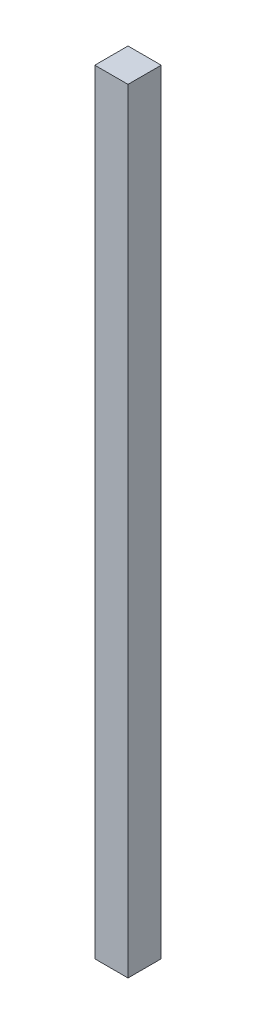
SolidWorks part; units mm, degrees
ref_plane "Plan de face" through (0, 0, 0) normal (0, 0, 1) x (1, 0, 0)
ref_plane "Plan de dessus" through (0, 0, 0) normal (0, 1, 0) x (1, 0, 0)
ref_plane "Plan de droite" through (0, 0, 0) normal (1, 0, 0) x (0, 0, -1)
sketch "Esquisse1" plane through (0, 0, 0) normal (0, 0, 1) x (1, 0, 0)
  line L1 (-41.6667, 69.6429) -> (-51.6667, 69.6429)
  line L2 (-41.6667, 69.6429) -> (-41.6667, -163.3571)
  line L3 (-41.6667, -163.3571) -> (-51.6667, -163.3571)
  line L4 (-51.6667, 69.6429) -> (-51.6667, -163.3571)
  dimension "D1" = 10
  dimension "D2" = 233
extrude "Boss.-Extru.1" add sketch "Esquisse1" along normal blind 10 contours L4 L3 L2 L1
equation "\"EpaisseurPlaque\"= 3"
equation "\"ProfondeurBoite\"=460"
equation "\"LongueurSyphon\"=170"
equation "\"LargeurSyphon\"=120"
equation "\"HauteurCoteDroit\"= 490"
equation "\"HauteurCoteGauche\"= 540"
equation "\"HauteurSolSyphon\"= 300"
equation "\"HauteurSyphon\"=\"HauteurCoteGauche\"-\"HauteurSolSyphon\""
equation "\"LargeurDroite\"=10"
equation "\"LargeurGauche\"=150"
equation "\"LargeurBoite\"= \"LargeurDroite\" + \"LargeurGauche\" + \"LargeurSyphon\""
equation "\"D2@Esquisse1\"=\"HauteurSyphon\" -7"
